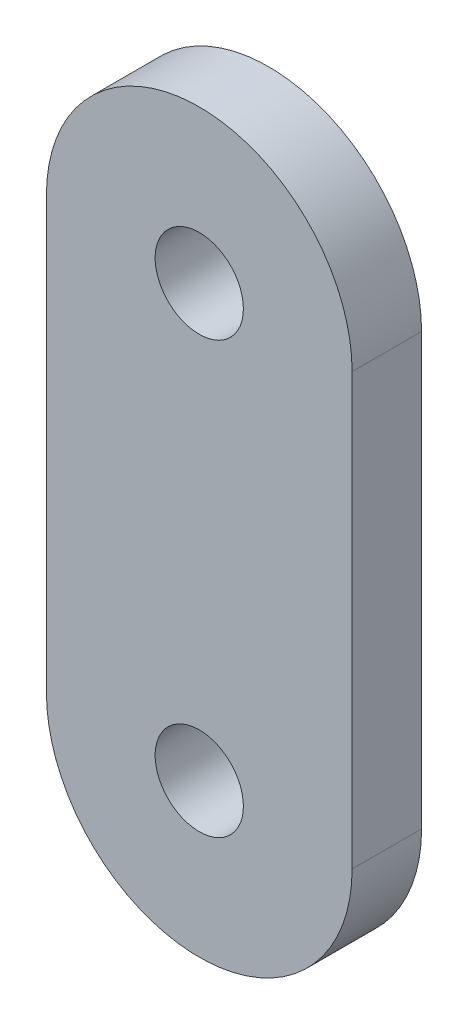
SolidWorks part; units mm, degrees
material "Plain Carbon Steel"
ref_plane "Front Plane" through (0, 0, 0) normal (0, 0, 1) x (1, 0, 0)
ref_plane "Top Plane" through (0, 0, 0) normal (0, 1, 0) x (1, 0, 0)
ref_plane "Right Plane" through (0, 0, 0) normal (1, 0, 0) x (0, 0, -1)
sketch "Sketch1" plane through (0, 0, 0) normal (0, 0, 1) x (1, 0, 0)
  line L0 (11, 0) -> (11, 31)
  line L1 (-11, 31) -> (-11, 0)
  arc A0 (-11, 0) -> (11, 0) centre (0, 0) ccw
  arc A1 (11, 31) -> (-11, 31) centre (0, 31) ccw
  circle A2 centre (0, 0) radius 3.175
  circle A3 centre (0, 31) radius 3.175
  dimension "D1" = 6.35
  dimension "D2" = 6.35
extrude "Boss-Extrude1" add sketch "Sketch1" along normal blind 5
